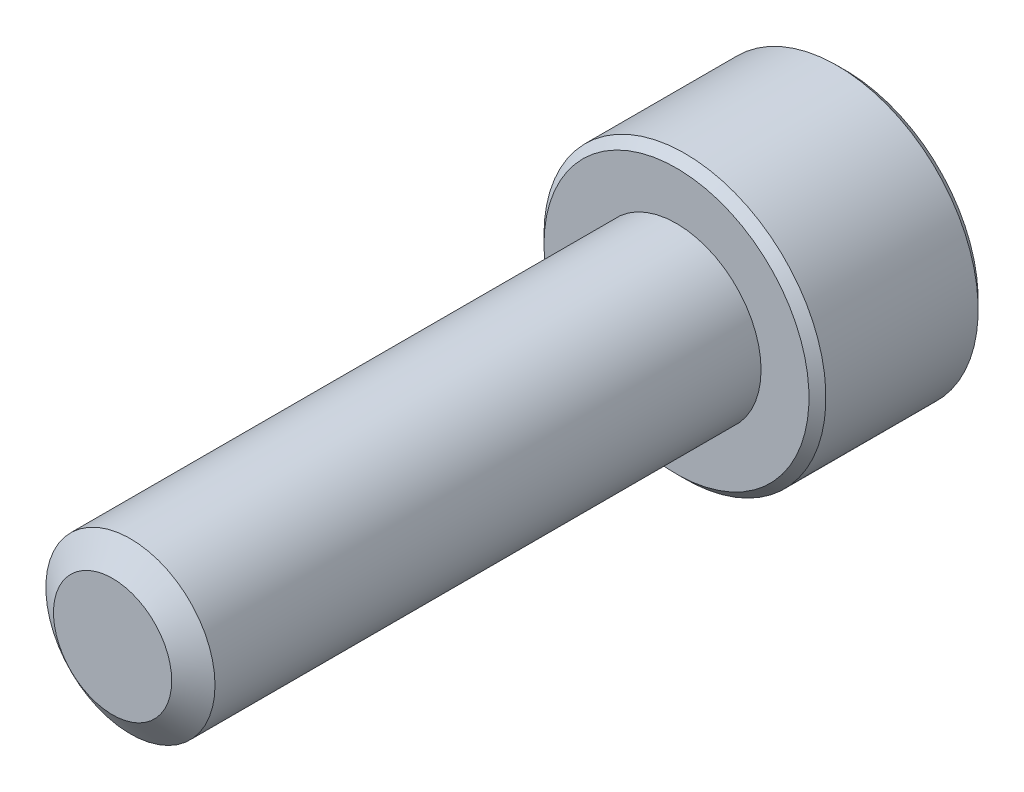
SolidWorks part; units mm, degrees
ref_plane "Front Plane" through (0, 0, 0) normal (0, 0, 1) x (1, 0, 0)
ref_plane "Top Plane" through (0, 0, 0) normal (0, 1, 0) x (1, 0, 0)
ref_plane "Right Plane" through (0, 0, 0) normal (1, 0, 0) x (0, 0, -1)
sketch "Sketch1" plane through (0, 0, 0) normal (0, 0, 1) x (1, 0, 0)
  circle A0 centre (0, 0) radius 3
  dimension "OD" = 6
extrude "Extrude1" add sketch "Sketch1" against normal blind 20
sketch "Sketch2" plane through (0, 0, 0) normal (0, 0, 1) x (1, 0, 0)
  circle A0 centre (0, 0) radius 3 construction
  circle A1 centre (0, 0) radius 3
curve "Helix/Spiral1" pitch 1 height 21 turns 21 parameters "pitch"=1
sketch "Sketch3" plane through (0, 0, 0) normal (1, 0, 0) x (0, 0, -1)
  line L0 (-0.875, 3) -> (-0.5, 2.3505)
  line L1 (-0.5, 2.3505) -> (-0.375, 2.3505)
  line L2 (-0.375, 2.3505) -> (0, 3)
  line L3 (-0.875, 3) -> (0, 3)
  line L4 (-0.4375, 3) -> (-0.4375, 2.3505) construction
  line L5 (-0.6875, 2.6752) -> (-0.1875, 2.6752) construction
  line L6 (0, 3) -> (0, -3) construction
  line L7 (0, -3) -> (20, -3) construction
  point P11 (4.5, -3)
  dimension "D1" = 0.125
  dimension "D2" = 0.5
  dimension "D3" = 60
  dimension "D4" = 4.5
sweep "Cut-Sweep1" [suppressed] cut profiles "Sketch3" path "Helix/Spiral1"
sketch "Sketch4" plane through (0, 0, 0) normal (1, 0, 0) x (0, 0, -1)
  line L0 (0.6327, 3) -> (0, 2.0965)
  line L1 (0, 2.0965) -> (0, 3)
  line L2 (0.6327, 3) -> (0, 3)
  line L3 (-0.875, 3) -> (0, 3) construction
  line L4 (0, 0) -> (7.0209, 0) construction
  dimension "D1" = 55
  dimension "D2" = 0.254
revolve "Cut-Revolve1" cut sketch "Sketch4" angle 360 about L4
sketch "Sketch5" [suppressed] plane through (0, 0, 0) normal (1, 0, 0) x (0, 0, -1)
  line L0 (20, -2.3644) -> (20, 2.1406) construction
  line L1 (20, 3) -> (0.1203, 3)
  line L2 (20, 3) -> (20, 0)
  line L3 (20, 0) -> (0.0001, 0)
  line L4 (0.0001, 2.6698) -> (0.0001, 0)
  line L5 (0.1203, 3) -> (0.0001, 2.6698)
  line L6 (0, 0) -> (9.9695, 0) construction
  point P3 (0.0001, 3)
  point P10 (0.0001, 3)
  dimension "D1" = 0.3302
  dimension "Thread min" = 0.0001
  dimension "D3" = 20
revolve "partially thread" [suppressed] add sketch "Sketch5" angle 360 about L6
sketch "Sketch6" plane through (0, 0, -20) normal (0, 0, -1) x (-1, 0, 0)
  circle A0 centre (0, 0) radius 5
  dimension "head dia" = 10
extrude "Extrude2" add sketch "Sketch6" along normal blind 6
sketch "Sketch7" plane through (0, 0, -26) normal (0, 0, -1) x (-1, 0, 0)
  line L1 (0, 2.8868) -> (-2.5, 1.4434)
  line L2 (-2.5, 1.4434) -> (-2.5, -1.4434)
  line L3 (-2.5, -1.4434) -> (0, -2.8868)
  line L4 (0, -2.8868) -> (2.5, -1.4434)
  line L5 (2.5, -1.4434) -> (2.5, 1.4434)
  line L6 (2.5, 1.4434) -> (0, 2.8868)
  circle A0 centre (0, 0) radius 2.5 construction
  dimension "hex dia" = 5
extrude "Cut-Extrude1" cut sketch "Sketch7" against normal blind 3.75
sketch "Sketch8" plane through (0, 0, -26) normal (0, 0, -1) x (-1, 0, 0)
  circle A0 centre (0, 0) radius 2.8868
extrude "Cut-Extrude2" cut sketch "Sketch8" against normal through all draft 45
chamfer "Chamfer1" distance 0.3 angle 45 2 edges at (-5, 0, -26) (-5, 0, -20)
sketch "Sketch9" plane through (0, 0, 0) normal (1, 0, 0) x (0, 0, -1)
  line L0 (0, 3) -> (0, -3) construction
  line L1 (5.5, 3) -> (5.5, -3) construction
  dimension "D1" = 5.5
sketch "Sketch10" plane through (0, 0, 0) normal (1, 0, 0) x (0, 0, -1)
  line L0 (20, 3) -> (20, 0)
  line L1 (20, 3) -> (19.75, 3)
  line L2 (19.75, 3) -> (18.5074, 0)
  line L3 (20, 0) -> (18.5074, 0)
  line L4 (20, 4.7) -> (20, -4.7) construction
  dimension "D1" = 22.5
  dimension "D2" = 0.25
revolve "Revolve1" add sketch "Sketch10" angle 360 about L3
equation "\"D3@Helix/Spiral1\" = \"screw length@Extrude1\"+\"pitch@Helix/Spiral1\""
equation "\"D1@Sketch3\" = \"pitch@Helix/Spiral1\"*.125"
equation "\"D2@Sketch3\" = \"pitch@Helix/Spiral1\"*.5"
equation "\"D1@Cut-Extrude1\" = \"hex dia@Sketch7\"*.75"
equation "\"D1@Chamfer1\" = \"head dia@Sketch6\"*.03"
equation "\"D1@Sketch9\" = \"pitch@Helix/Spiral1\"*5.5"
equation "\"D2@Sketch10\" = \"pitch@Helix/Spiral1\"*.25"
equation "\"D4@Sketch3\" = \"pitch@Helix/Spiral1\"*4.50"
